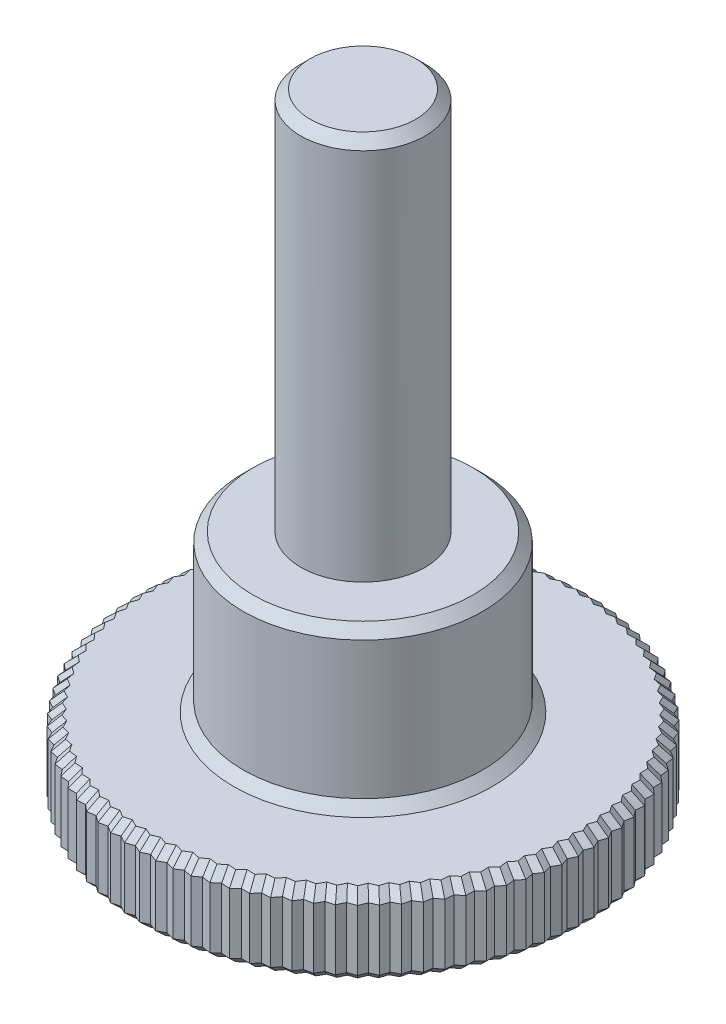
SolidWorks part; units mm, degrees
material "AISI 1020"
ref_plane "Front Plane" through (0, 0, 0) normal (0, 0, 1) x (1, 0, 0)
ref_plane "Top Plane" through (0, 0, 0) normal (0, 1, 0) x (1, 0, 0)
ref_plane "Right Plane" through (0, 0, 0) normal (1, 0, 0) x (0, 0, -1)
sketch "Sketch1" plane through (0, 0, 0) normal (0, 1, 0) x (1, 0, 0)
  line L0 (0, 0) -> (0, 7) construction
  line L1 (0, 7) -> (0.2406, 6.8908)
  line L2 (0.4883, 6.9829) -> (0.2406, 6.8908)
  line L3 (0.2443, 6.9957) -> (0, 0) construction
  line L4 (0.4883, 6.9829) -> (0.7207, 6.8573)
  line L5 (0.9742, 6.9319) -> (0.7207, 6.8573)
  line L6 (0.9742, 6.9319) -> (1.1973, 6.7903)
  line L7 (1.4554, 6.847) -> (1.1973, 6.7903)
  line L8 (1.4554, 6.847) -> (1.6681, 6.6902)
  line L9 (1.9295, 6.7288) -> (1.6681, 6.6902)
  line L10 (1.9295, 6.7288) -> (2.1307, 6.5576)
  line L11 (2.3941, 6.5778) -> (2.1307, 6.5576)
  line L12 (2.3941, 6.5778) -> (2.5829, 6.393)
  line L13 (2.8472, 6.3948) -> (2.5829, 6.393)
  line L14 (2.8472, 6.3948) -> (3.0226, 6.1972)
  line L15 (3.2863, 6.1806) -> (3.0226, 6.1972)
  line L16 (3.2863, 6.1806) -> (3.4475, 5.9713)
  line L17 (3.7094, 5.9363) -> (3.4475, 5.9713)
  line L18 (3.7094, 5.9363) -> (3.8557, 5.7163)
  line L19 (4.1145, 5.6631) -> (3.8557, 5.7163)
  line L20 (4.1145, 5.6631) -> (4.245, 5.4334)
  line L21 (4.4995, 5.3623) -> (4.245, 5.4334)
  line L22 (4.4995, 5.3623) -> (4.6137, 5.124)
  line L23 (4.8626, 5.0354) -> (4.6137, 5.124)
  line L24 (4.8626, 5.0354) -> (4.9599, 4.7897)
  line L25 (5.202, 4.6839) -> (4.9599, 4.7897)
  line L26 (5.202, 4.6839) -> (5.2819, 4.4321)
  line L27 (5.5161, 4.3096) -> (5.2819, 4.4321)
  line L28 (5.5161, 4.3096) -> (5.5782, 4.0528)
  line L29 (5.8033, 3.9144) -> (5.5782, 4.0528)
  line L30 (5.8033, 3.9144) -> (5.8473, 3.6538)
  line L31 (6.0622, 3.5) -> (5.8473, 3.6538)
  line L32 (6.0622, 3.5) -> (6.088, 3.237)
  line L33 (6.2916, 3.0686) -> (6.088, 3.237)
  line L34 (6.2916, 3.0686) -> (6.2989, 2.8045)
  line L35 (6.4903, 2.6222) -> (6.2989, 2.8045)
  line L36 (6.4903, 2.6222) -> (6.4792, 2.3582)
  line L37 (6.6574, 2.1631) -> (6.4792, 2.3582)
  line L38 (6.6574, 2.1631) -> (6.6279, 1.9005)
  line L39 (6.7921, 1.6935) -> (6.6279, 1.9005)
  line L40 (6.7921, 1.6935) -> (6.7444, 1.4336)
  line L41 (6.8937, 1.2155) -> (6.7444, 1.4336)
  line L42 (6.8937, 1.2155) -> (6.8279, 0.9596)
  line L43 (6.9617, 0.7317) -> (6.8279, 0.9596)
  line L44 (6.9617, 0.7317) -> (6.8783, 0.481)
  line L45 (6.9957, 0.2443) -> (6.8783, 0.481)
  line L46 (6.9957, 0.2443) -> (6.895, 0)
  line L47 (6.9957, -0.2443) -> (6.895, 0)
  line L48 (6.9957, -0.2443) -> (6.8783, -0.481)
  line L49 (6.9617, -0.7317) -> (6.8783, -0.481)
  line L50 (6.9617, -0.7317) -> (6.8279, -0.9596)
  line L51 (6.8937, -1.2155) -> (6.8279, -0.9596)
  line L52 (6.8937, -1.2155) -> (6.7444, -1.4336)
  line L53 (6.7921, -1.6935) -> (6.7444, -1.4336)
  line L54 (6.7921, -1.6935) -> (6.6279, -1.9005)
  line L55 (6.6574, -2.1631) -> (6.6279, -1.9005)
  line L56 (6.6574, -2.1631) -> (6.4792, -2.3582)
  line L57 (6.4903, -2.6222) -> (6.4792, -2.3582)
  line L58 (6.4903, -2.6222) -> (6.2989, -2.8045)
  line L59 (6.2916, -3.0686) -> (6.2989, -2.8045)
  line L60 (6.2916, -3.0686) -> (6.088, -3.237)
  line L61 (6.0622, -3.5) -> (6.088, -3.237)
  line L62 (6.0622, -3.5) -> (5.8473, -3.6538)
  line L63 (5.8033, -3.9144) -> (5.8473, -3.6538)
  line L64 (5.8033, -3.9144) -> (5.5782, -4.0528)
  line L65 (5.5161, -4.3096) -> (5.5782, -4.0528)
  line L66 (5.5161, -4.3096) -> (5.2819, -4.4321)
  line L67 (5.202, -4.6839) -> (5.2819, -4.4321)
  line L68 (5.202, -4.6839) -> (4.9599, -4.7897)
  line L69 (4.8626, -5.0354) -> (4.9599, -4.7897)
  line L70 (4.8626, -5.0354) -> (4.6137, -5.124)
  line L71 (4.4995, -5.3623) -> (4.6137, -5.124)
  line L72 (4.4995, -5.3623) -> (4.245, -5.4334)
  line L73 (4.1145, -5.6631) -> (4.245, -5.4334)
  line L74 (4.1145, -5.6631) -> (3.8557, -5.7163)
  line L75 (3.7094, -5.9363) -> (3.8557, -5.7163)
  line L76 (3.7094, -5.9363) -> (3.4475, -5.9713)
  line L77 (3.2863, -6.1806) -> (3.4475, -5.9713)
  line L78 (3.2863, -6.1806) -> (3.0226, -6.1972)
  line L79 (2.8472, -6.3948) -> (3.0226, -6.1972)
  line L80 (2.8472, -6.3948) -> (2.5829, -6.393)
  line L81 (2.3941, -6.5778) -> (2.5829, -6.393)
  line L82 (2.3941, -6.5778) -> (2.1307, -6.5576)
  line L83 (1.9295, -6.7288) -> (2.1307, -6.5576)
  line L84 (1.9295, -6.7288) -> (1.6681, -6.6902)
  line L85 (1.4554, -6.847) -> (1.6681, -6.6902)
  line L86 (1.4554, -6.847) -> (1.1973, -6.7903)
  line L87 (0.9742, -6.9319) -> (1.1973, -6.7903)
  line L88 (0.9742, -6.9319) -> (0.7207, -6.8573)
  line L89 (0.4883, -6.9829) -> (0.7207, -6.8573)
  line L90 (0.4883, -6.9829) -> (0.2406, -6.8908)
  line L91 (0, -7) -> (0.2406, -6.8908)
  line L92 (0, -7) -> (-0.2406, -6.8908)
  line L93 (-0.4883, -6.9829) -> (-0.2406, -6.8908)
  line L94 (-0.4883, -6.9829) -> (-0.7207, -6.8573)
  line L95 (-0.9742, -6.9319) -> (-0.7207, -6.8573)
  line L96 (-0.9742, -6.9319) -> (-1.1973, -6.7903)
  line L97 (-1.4554, -6.847) -> (-1.1973, -6.7903)
  line L98 (-1.4554, -6.847) -> (-1.6681, -6.6902)
  line L99 (-1.9295, -6.7288) -> (-1.6681, -6.6902)
  line L100 (-1.9295, -6.7288) -> (-2.1307, -6.5576)
  line L101 (-2.3941, -6.5778) -> (-2.1307, -6.5576)
  line L102 (-2.3941, -6.5778) -> (-2.5829, -6.393)
  line L103 (-2.8472, -6.3948) -> (-2.5829, -6.393)
  line L104 (-2.8472, -6.3948) -> (-3.0226, -6.1972)
  line L105 (-3.2863, -6.1806) -> (-3.0226, -6.1972)
  line L106 (-3.2863, -6.1806) -> (-3.4475, -5.9713)
  line L107 (-3.7094, -5.9363) -> (-3.4475, -5.9713)
  line L108 (-3.7094, -5.9363) -> (-3.8557, -5.7163)
  line L109 (-4.1145, -5.6631) -> (-3.8557, -5.7163)
  line L110 (-4.1145, -5.6631) -> (-4.245, -5.4334)
  line L111 (-4.4995, -5.3623) -> (-4.245, -5.4334)
  line L112 (-4.4995, -5.3623) -> (-4.6137, -5.124)
  line L113 (-4.8626, -5.0354) -> (-4.6137, -5.124)
  line L114 (-4.8626, -5.0354) -> (-4.9599, -4.7897)
  line L115 (-5.202, -4.6839) -> (-4.9599, -4.7897)
  line L116 (-5.202, -4.6839) -> (-5.2819, -4.4321)
  line L117 (-5.5161, -4.3096) -> (-5.2819, -4.4321)
  line L118 (-5.5161, -4.3096) -> (-5.5782, -4.0528)
  line L119 (-5.8033, -3.9144) -> (-5.5782, -4.0528)
  line L120 (-5.8033, -3.9144) -> (-5.8473, -3.6538)
  line L121 (-6.0622, -3.5) -> (-5.8473, -3.6538)
  line L122 (-6.0622, -3.5) -> (-6.088, -3.237)
  line L123 (-6.2916, -3.0686) -> (-6.088, -3.237)
  line L124 (-6.2916, -3.0686) -> (-6.2989, -2.8045)
  line L125 (-6.4903, -2.6222) -> (-6.2989, -2.8045)
  line L126 (-6.4903, -2.6222) -> (-6.4792, -2.3582)
  line L127 (-6.6574, -2.1631) -> (-6.4792, -2.3582)
  line L128 (-6.6574, -2.1631) -> (-6.6279, -1.9005)
  line L129 (-6.7921, -1.6935) -> (-6.6279, -1.9005)
  line L130 (-6.7921, -1.6935) -> (-6.7444, -1.4336)
  line L131 (-6.8937, -1.2155) -> (-6.7444, -1.4336)
  line L132 (-6.8937, -1.2155) -> (-6.8279, -0.9596)
  line L133 (-6.9617, -0.7317) -> (-6.8279, -0.9596)
  line L134 (-6.9617, -0.7317) -> (-6.8783, -0.481)
  line L135 (-6.9957, -0.2443) -> (-6.8783, -0.481)
  line L136 (-6.9957, -0.2443) -> (-6.895, 0)
  line L137 (-6.9957, 0.2443) -> (-6.895, 0)
  line L138 (-6.9957, 0.2443) -> (-6.8783, 0.481)
  line L139 (-6.9617, 0.7317) -> (-6.8783, 0.481)
  line L140 (-6.9617, 0.7317) -> (-6.8279, 0.9596)
  line L141 (-6.8937, 1.2155) -> (-6.8279, 0.9596)
  line L142 (-6.8937, 1.2155) -> (-6.7444, 1.4336)
  line L143 (-6.7921, 1.6935) -> (-6.7444, 1.4336)
  line L144 (-6.7921, 1.6935) -> (-6.6279, 1.9005)
  line L145 (-6.6574, 2.1631) -> (-6.6279, 1.9005)
  line L146 (-6.6574, 2.1631) -> (-6.4792, 2.3582)
  line L147 (-6.4903, 2.6222) -> (-6.4792, 2.3582)
  line L148 (-6.4903, 2.6222) -> (-6.2989, 2.8045)
  line L149 (-6.2916, 3.0686) -> (-6.2989, 2.8045)
  line L150 (-6.2916, 3.0686) -> (-6.088, 3.237)
  line L151 (-6.0622, 3.5) -> (-6.088, 3.237)
  line L152 (-6.0622, 3.5) -> (-5.8473, 3.6538)
  line L153 (-5.8033, 3.9144) -> (-5.8473, 3.6538)
  line L154 (-5.8033, 3.9144) -> (-5.5782, 4.0528)
  line L155 (-5.5161, 4.3096) -> (-5.5782, 4.0528)
  line L156 (-5.5161, 4.3096) -> (-5.2819, 4.4321)
  line L157 (-5.202, 4.6839) -> (-5.2819, 4.4321)
  line L158 (-5.202, 4.6839) -> (-4.9599, 4.7897)
  line L159 (-4.8626, 5.0354) -> (-4.9599, 4.7897)
  line L160 (-4.8626, 5.0354) -> (-4.6137, 5.124)
  line L161 (-4.4995, 5.3623) -> (-4.6137, 5.124)
  line L162 (-4.4995, 5.3623) -> (-4.245, 5.4334)
  line L163 (-4.1145, 5.6631) -> (-4.245, 5.4334)
  line L164 (-4.1145, 5.6631) -> (-3.8557, 5.7163)
  line L165 (-3.7094, 5.9363) -> (-3.8557, 5.7163)
  line L166 (-3.7094, 5.9363) -> (-3.4475, 5.9713)
  line L167 (-3.2863, 6.1806) -> (-3.4475, 5.9713)
  line L168 (-3.2863, 6.1806) -> (-3.0226, 6.1972)
  line L169 (-2.8472, 6.3948) -> (-3.0226, 6.1972)
  line L170 (-2.8472, 6.3948) -> (-2.5829, 6.393)
  line L171 (-2.3941, 6.5778) -> (-2.5829, 6.393)
  line L172 (-2.3941, 6.5778) -> (-2.1307, 6.5576)
  line L173 (-1.9295, 6.7288) -> (-2.1307, 6.5576)
  line L174 (-1.9295, 6.7288) -> (-1.6681, 6.6902)
  line L175 (-1.4554, 6.847) -> (-1.6681, 6.6902)
  line L176 (-1.4554, 6.847) -> (-1.1973, 6.7903)
  line L177 (-0.9742, 6.9319) -> (-1.1973, 6.7903)
  line L178 (-0.9742, 6.9319) -> (-0.7207, 6.8573)
  line L179 (-0.4883, 6.9829) -> (-0.7207, 6.8573)
  line L180 (-0.4883, 6.9829) -> (-0.2406, 6.8908)
  line L181 (0, 7) -> (-0.2406, 6.8908)
  circle A0 centre (0, 0) radius 7
  dimension "D1" = 14
  dimension "D2" = 2
  dimension "D3" = 90
extrude "Extrude1" add sketch "Sketch1" along normal blind 2.5 contours L1 L181 L180 L179 L178 L177 L176 L175 L174 L173 L172 L171 L170 L169 L168 L167 L166 L165 L164 L163 L162 L161 L160 L159 L158 L157 L156 L155 L154 L153 L152 L151 L150 L149 L148 L147 L146 L145 L144 L143 L142 L141 L140 L139 L138 L137 L136 L135 L134 L133 L132
sketch "Sketch2" plane through (0, 2.5, 0) normal (0, 1, 0) x (1, 0, 0)
  circle A0 centre (0, 0) radius 3.75
  dimension "D1" = 7.5
extrude "Extrude2" add sketch "Sketch2" along normal blind 4.9
sketch "Sketch3" plane through (0, 7.4, 0) normal (0, 1, 0) x (1, 0, 0)
  circle A0 centre (0, 0) radius 1.95
  dimension "D1" = 3.9
extrude "Extrude3" add sketch "Sketch3" along normal blind 12
cosmetic thread "Cosmetic Thread1" parameters "D2"=1.993
chamfer "Chamfer1" distance 0.3 angle 45 363 edges at (0.3645, 2.5, -6.9369) (0.6045, 2.5, -6.9201) (0.8475, 2.5, -6.8946) (1.0858, 2.5, -6.8611) (1.3263, 2.5, -6.8187) (1.5617, 2.5, -6.7686) (1.7988, 2.5, -6.7095) (2.0301, 2.5, -6.6432) (2.2624, 2.5, -6.5677) (2.4885, 2.5, -6.4854) (2.715, 2.5, -6.3939) (2.9349, 2.5, -6.296) (3.1544, 2.5, -6.1889) (3.3669, 2.5, -6.076) (3.5785, 2.5, -5.9538) (3.7825, 2.5, -5.8263) (3.9851, 2.5, -5.6897) (4.1798, 2.5, -5.5482) (4.3723, 2.5, -5.3978) (4.5566, 2.5, -5.2432) (4.7381, 2.5, -5.0797) (4.9112, 2.5, -4.9125) (5.0809, 2.5, -4.7368) (5.242, 2.5, -4.558) (5.399, 2.5, -4.3708) (5.5471, 2.5, -4.1812) (5.6907, 2.5, -3.9836) (5.8253, 2.5, -3.7841) (5.9548, 2.5, -3.5769) (6.0751, 2.5, -3.3685) (6.1898, 2.5, -3.1528) (6.2952, 2.5, -2.9365) (6.3946, 2.5, -2.7134) (6.4848, 2.5, -2.4902) (6.5683, 2.5, -2.2607) (6.6427, 2.5, -2.0318) (6.71, 2.5, -1.797) (6.7682, 2.5, -1.5635) (6.819, 2.5, -1.3245) (6.8608, 2.5, -1.0876) (6.8948, 2.5, -0.8457) (6.92, 2.5, -0.6063) (6.937, 2.5, -0.3626) (6.9454, 2.5, -0.1221) (6.9454, 2.5, 0.1221) (6.937, 2.5, 0.3626) (6.92, 2.5, 0.6063) (6.8948, 2.5, 0.8457) (6.8608, 2.5, 1.0876) (6.819, 2.5, 1.3245) (6.7682, 2.5, 1.5635) (6.71, 2.5, 1.797) (6.6427, 2.5, 2.0318) (6.5683, 2.5, 2.2607) (6.4848, 2.5, 2.4902) (6.3946, 2.5, 2.7134) (6.2952, 2.5, 2.9365) (6.1898, 2.5, 3.1528) (6.0751, 2.5, 3.3685) (5.9548, 2.5, 3.5769) (5.8253, 2.5, 3.7841) (5.6907, 2.5, 3.9836) (5.5471, 2.5, 4.1812) (5.399, 2.5, 4.3708) (5.242, 2.5, 4.558) (5.0809, 2.5, 4.7368) (4.9112, 2.5, 4.9125) (4.7381, 2.5, 5.0797) (4.5566, 2.5, 5.2432) (4.3723, 2.5, 5.3978) (4.1798, 2.5, 5.5482) (3.9851, 2.5, 5.6897) (3.7825, 2.5, 5.8263) (3.5785, 2.5, 5.9538) (3.3669, 2.5, 6.076) (3.1544, 2.5, 6.1889) (2.9349, 2.5, 6.296) (2.715, 2.5, 6.3939) (2.4885, 2.5, 6.4854) (2.2624, 2.5, 6.5677) (2.0301, 2.5, 6.6432) (1.7988, 2.5, 6.7095) (1.5617, 2.5, 6.7686) (1.3263, 2.5, 6.8187) (1.0858, 2.5, 6.8611) (0.8475, 2.5, 6.8946) (0.6045, 2.5, 6.9201) (0.3645, 2.5, 6.9369) (0.1203, 2.5, 6.9454) (-0.1203, 2.5, 6.9454) (-0.3645, 2.5, 6.9369) (-0.6045, 2.5, 6.9201) (-0.8475, 2.5, 6.8946) (-1.0858, 2.5, 6.8611) (-1.3263, 2.5, 6.8187) (-1.5617, 2.5, 6.7686) (-1.7988, 2.5, 6.7095) (-2.0301, 2.5, 6.6432) (-2.2624, 2.5, 6.5677) (-2.4885, 2.5, 6.4854) (-2.715, 2.5, 6.3939) (-2.9349, 2.5, 6.296) (-3.1544, 2.5, 6.1889) (-3.3669, 2.5, 6.076) (-3.5785, 2.5, 5.9538) (-3.7825, 2.5, 5.8263) (-3.9851, 2.5, 5.6897) (-4.1798, 2.5, 5.5482) (-4.3723, 2.5, 5.3978) (-4.5566, 2.5, 5.2432) (-4.7381, 2.5, 5.0797) (-4.9112, 2.5, 4.9125) (-5.0809, 2.5, 4.7368) (-5.242, 2.5, 4.558) (-5.399, 2.5, 4.3708) (-5.5471, 2.5, 4.1812) (-5.6907, 2.5, 3.9836) (-5.8253, 2.5, 3.7841) (-5.9548, 2.5, 3.5769) (-6.0751, 2.5, 3.3685) (-6.1898, 2.5, 3.1528) (-6.2952, 2.5, 2.9365) (-6.3946, 2.5, 2.7134) (-6.4848, 2.5, 2.4902) (-6.5683, 2.5, 2.2607) (-6.6427, 2.5, 2.0318) (-6.71, 2.5, 1.797) (-6.7682, 2.5, 1.5635) (-6.819, 2.5, 1.3245) (-6.8608, 2.5, 1.0876) (-6.8948, 2.5, 0.8457) (-6.92, 2.5, 0.6063) (-6.937, 2.5, 0.3626) (-6.9454, 2.5, 0.1221) (-6.9454, 2.5, -0.1221) (-6.937, 2.5, -0.3626) (-6.92, 2.5, -0.6063) (-6.8948, 2.5, -0.8457) (-6.8608, 2.5, -1.0876) (-6.819, 2.5, -1.3245) (-6.7682, 2.5, -1.5635) (-6.71, 2.5, -1.797) (-6.6427, 2.5, -2.0318) (-6.5683, 2.5, -2.2607) (-6.4848, 2.5, -2.4902) (-6.3946, 2.5, -2.7134) (-6.2952, 2.5, -2.9365) (-6.1898, 2.5, -3.1528) (-6.0751, 2.5, -3.3685) (-5.9548, 2.5, -3.5769) (-5.8253, 2.5, -3.7841) (-5.6907, 2.5, -3.9836) (-5.5471, 2.5, -4.1812) (-5.399, 2.5, -4.3708) (-5.242, 2.5, -4.558) (-5.0809, 2.5, -4.7368) (-4.9112, 2.5, -4.9125) (-4.7381, 2.5, -5.0797) (-4.5566, 2.5, -5.2432) (-4.3723, 2.5, -5.3978) (-4.1798, 2.5, -5.5482) (-3.9851, 2.5, -5.6897) (-3.7825, 2.5, -5.8263) (-3.5785, 2.5, -5.9538) (-3.3669, 2.5, -6.076) (-3.1544, 2.5, -6.1889) (-2.9349, 2.5, -6.296) (-2.715, 2.5, -6.3939) (-2.4885, 2.5, -6.4854) (-2.2624, 2.5, -6.5677) (-2.0301, 2.5, -6.6432) (-1.7988, 2.5, -6.7095) (-1.5617, 2.5, -6.7686) (-1.3263, 2.5, -6.8187) (-1.0858, 2.5, -6.8611) (-0.8475, 2.5, -6.8946) (-0.6045, 2.5, -6.9201) (-0.3645, 2.5, -6.9369) (-0.1203, 2.5, -6.9454) (0.1203, 2.5, -6.9454) (0, 2.5, 3.75) (-0.1203, 0, -6.9454) (-0.3645, 0, -6.9369) (-0.6045, 0, -6.9201) (-0.8475, 0, -6.8946) (-1.0858, 0, -6.8611) (-1.3263, 0, -6.8187) (-1.5617, 0, -6.7686) (-1.7988, 0, -6.7095) (-2.0301, 0, -6.6432) (-2.2624, 0, -6.5677) (-2.4885, 0, -6.4854) (-2.715, 0, -6.3939) (-2.9349, 0, -6.296) (-3.1544, 0, -6.1889) (-3.3669, 0, -6.076) (-3.5785, 0, -5.9538) (-3.7825, 0, -5.8263) (-3.9851, 0, -5.6897) (-4.1798, 0, -5.5482) (-4.3723, 0, -5.3978) (-4.5566, 0, -5.2432) (-4.7381, 0, -5.0797) (-4.9112, 0, -4.9125) (-5.0809, 0, -4.7368) (-5.242, 0, -4.558) (-5.399, 0, -4.3708) (-5.5471, 0, -4.1812) (-5.6907, 0, -3.9836) (-5.8253, 0, -3.7841) (-5.9548, 0, -3.5769) (-6.0751, 0, -3.3685) (-6.1898, 0, -3.1528) (-6.2952, 0, -2.9365) (-6.3946, 0, -2.7134) (-6.4848, 0, -2.4902) (-6.5683, 0, -2.2607) (-6.6427, 0, -2.0318) (-6.71, 0, -1.797) (-6.7682, 0, -1.5635) (-6.819, 0, -1.3245) (-6.8608, 0, -1.0876) (-6.8948, 0, -0.8457) (-6.92, 0, -0.6063) (-6.937, 0, -0.3626) (-6.9454, 0, -0.1221) (-6.9454, 0, 0.1221) (-6.937, 0, 0.3626) (-6.92, 0, 0.6063) (-6.8948, 0, 0.8457) (-6.8608, 0, 1.0876) (-6.819, 0, 1.3245) (-6.7682, 0, 1.5635) (-6.71, 0, 1.797) (-6.6427, 0, 2.0318) (-6.5683, 0, 2.2607) (-6.4848, 0, 2.4902) (-6.3946, 0, 2.7134) (-6.2952, 0, 2.9365) (-6.1898, 0, 3.1528) (-6.0751, 0, 3.3685) (-5.9548, 0, 3.5769) (-5.8253, 0, 3.7841) (-5.6907, 0, 3.9836) (-5.5471, 0, 4.1812) (-5.399, 0, 4.3708) (-5.242, 0, 4.558) (-5.0809, 0, 4.7368) (-4.9112, 0, 4.9125) (-4.7381, 0, 5.0797) (-4.5566, 0, 5.2432) (-4.3723, 0, 5.3978) (-4.1798, 0, 5.5482) (-3.9851, 0, 5.6897) (-3.7825, 0, 5.8263) (-3.5785, 0, 5.9538) (-3.3669, 0, 6.076) (-3.1544, 0, 6.1889) (-2.9349, 0, 6.296) (-2.715, 0, 6.3939) (-2.4885, 0, 6.4854) (-2.2624, 0, 6.5677) (-2.0301, 0, 6.6432) (-1.7988, 0, 6.7095) (-1.5617, 0, 6.7686) (-1.3263, 0, 6.8187) (-1.0858, 0, 6.8611) (-0.8475, 0, 6.8946) (-0.6045, 0, 6.9201) (-0.3645, 0, 6.9369) (-0.1203, 0, 6.9454) (0.1203, 0, 6.9454) (0.3645, 0, 6.9369) (0.6045, 0, 6.9201) (0.8475, 0, 6.8946) (1.0858, 0, 6.8611) (1.3263, 0, 6.8187) (1.5617, 0, 6.7686) (1.7988, 0, 6.7095) (2.0301, 0, 6.6432) (2.2624, 0, 6.5677) (2.4885, 0, 6.4854) (2.715, 0, 6.3939) (2.9349, 0, 6.296) (3.1544, 0, 6.1889) (3.3669, 0, 6.076) (3.5785, 0, 5.9538) (3.7825, 0, 5.8263) (3.9851, 0, 5.6897) (4.1798, 0, 5.5482) (4.3723, 0, 5.3978) (4.5566, 0, 5.2432) (4.7381, 0, 5.0797) (4.9112, 0, 4.9125) (5.0809, 0, 4.7368) (5.242, 0, 4.558) (5.399, 0, 4.3708) (5.5471, 0, 4.1812) (5.6907, 0, 3.9836) (5.8253, 0, 3.7841) (5.9548, 0, 3.5769) (6.0751, 0, 3.3685) (6.1898, 0, 3.1528) (6.2952, 0, 2.9365) (6.3946, 0, 2.7134) (6.4848, 0, 2.4902) (6.5683, 0, 2.2607) (6.6427, 0, 2.0318) (6.71, 0, 1.797) (6.7682, 0, 1.5635) (6.819, 0, 1.3245) (6.8608, 0, 1.0876) (6.8948, 0, 0.8457) (6.92, 0, 0.6063) (6.937, 0, 0.3626) (6.9454, 0, 0.1221) (6.9454, 0, -0.1221) (6.937, 0, -0.3626) (6.92, 0, -0.6063) (6.8948, 0, -0.8457) (6.8608, 0, -1.0876) (6.819, 0, -1.3245) (6.7682, 0, -1.5635) (6.71, 0, -1.797) (6.6427, 0, -2.0318) (6.5683, 0, -2.2607) (6.4848, 0, -2.4902) (6.3946, 0, -2.7134) (6.2952, 0, -2.9365) (6.1898, 0, -3.1528) (6.0751, 0, -3.3685) (5.9548, 0, -3.5769) (5.8253, 0, -3.7841) (5.6907, 0, -3.9836) (5.5471, 0, -4.1812) (5.399, 0, -4.3708) (5.242, 0, -4.558) (5.0809, 0, -4.7368) (4.9112, 0, -4.9125) (4.7381, 0, -5.0797) (4.5566, 0, -5.2432) (4.3723, 0, -5.3978) (4.1798, 0, -5.5482) (3.9851, 0, -5.6897) (3.7825, 0, -5.8263) (3.5785, 0, -5.9538) (3.3669, 0, -6.076) (3.1544, 0, -6.1889) (2.9349, 0, -6.296) (2.715, 0, -6.3939) (2.4885, 0, -6.4854) (2.2624, 0, -6.5677) (2.0301, 0, -6.6432) (1.7988, 0, -6.7095) (1.5617, 0, -6.7686) (1.3263, 0, -6.8187) (1.0858, 0, -6.8611) (0.8475, 0, -6.8946) (0.6045, 0, -6.9201) (0.3645, 0, -6.9369) (0.1203, 0, -6.9454) (0, 19.4, 1.95) (0, 7.4, 3.75)
